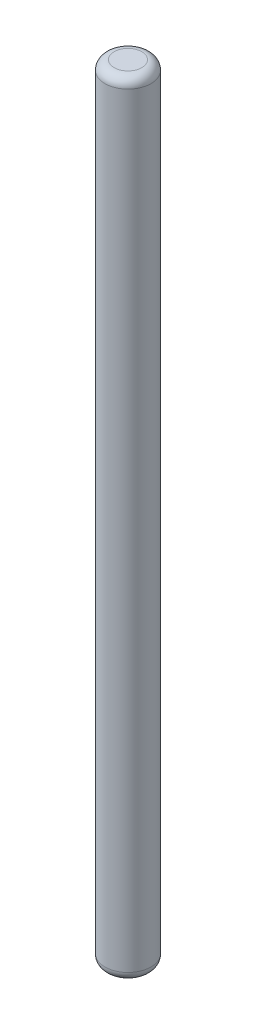
SolidWorks part; units mm, degrees
ref_plane "Front Plane" through (0, 0, 0) normal (0, 0, 1) x (1, 0, 0)
ref_plane "Top Plane" through (0, 0, 0) normal (0, 1, 0) x (1, 0, 0)
ref_plane "Right Plane" through (0, 0, 0) normal (1, 0, 0) x (0, 0, -1)
sketch "Sketch2" plane through (0, 0, 0) normal (0, 1, 0) x (1, 0, 0)
  circle A0 centre (0.0611, 0.0611) radius 2.5
  dimension "D1" = 5
extrude "Boss-Extrude1" add sketch "Sketch2" along normal blind 85
sketch "Sketch3" plane through (0, 85, 0) normal (0, 1, 0) x (1, 0, 0)
  line L0 (-1.0063, 2.3218) -> (1.1731, 2.3001)
  arc A0 (1.1731, 2.3001) -> (-1.0063, 2.3218) centre (0.0611, 0.0611) ccw
  circle A1 centre (0.0611, 0.0611) radius 2.5 construction
  dimension "D1" = 5
  dimension "D2" = 0
  dimension "D3" = 2.25
extrude "Cut-Extrude1" cut sketch "Sketch3" against normal blind 25
fillet "Fillet1" radius 1 1 edges at (0.0362, 85, 2.4388)
fillet "Fillet2" radius 1 1 edges at (0.0611, 0, 2.4389)
